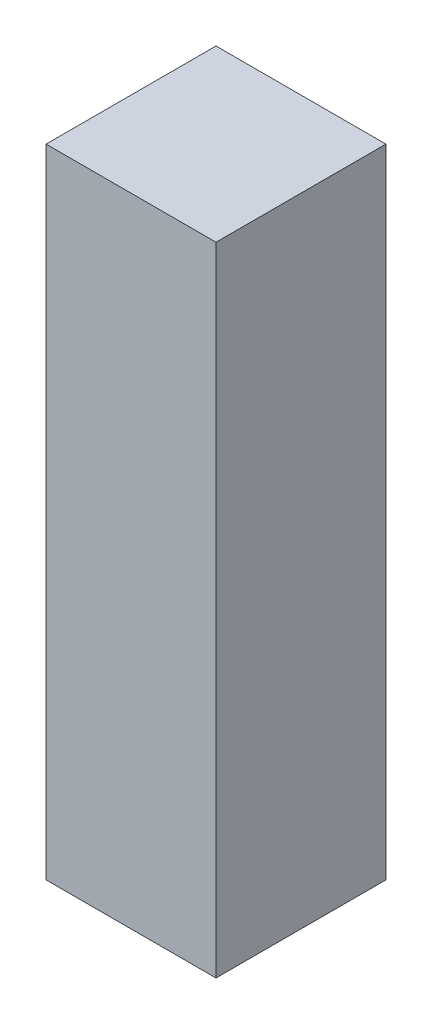
SolidWorks part; units mm, degrees
ref_plane "Front Plane" through (0, 0, 0) normal (0, 0, 1) x (1, 0, 0)
ref_plane "Top Plane" through (0, 0, 0) normal (0, 1, 0) x (1, 0, 0)
ref_plane "Right Plane" through (0, 0, 0) normal (1, 0, 0) x (0, 0, -1)
sketch "Sketch1" plane through (0, 0, 0) normal (0, 1, 0) x (1, 0, 0)
  line L0 (14.2053, 54.4102) -> (14.2053, 20.5435) construction
  line L1 (-36.5947, 54.4102) -> (65.0053, 54.4102)
  line L2 (-36.5947, 54.4102) -> (-36.5947, -47.1898)
  line L3 (-36.5947, -47.1898) -> (65.0053, -47.1898)
  line L4 (65.0053, 54.4102) -> (65.0053, -47.1898)
  line L5 (14.2053, -47.1898) -> (14.2053, -13.3232) construction
  dimension "D1" = 101.6
  dimension "D2" = 101.6
extrude "Boss-Extrude1" add sketch "Sketch1" against normal blind 381
